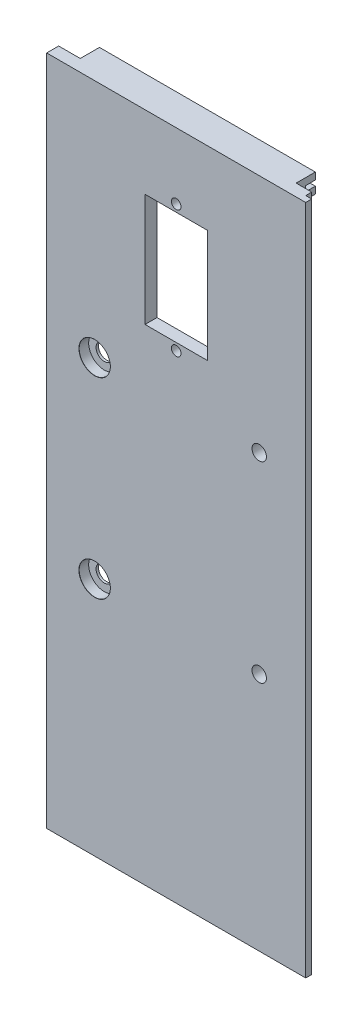
SolidWorks part; units mm, degrees
ref_plane "Plano frontal" through (0, 0, 0) normal (0, 0, 1) x (1, 0, 0)
ref_plane "Plano superior" through (0, 0, 0) normal (0, 1, 0) x (1, 0, 0)
ref_plane "Plano direito" through (0, 0, 0) normal (1, 0, 0) x (0, 0, -1)
other "Centro da massa"
sketch "Esboço1" plane through (0, 0, 0) normal (0, 0, 1) x (1, 0, 0)
  line L1 (-15.8914, 40.0685) -> (38.1086, 40.0685)
  line L2 (-15.8914, 40.0685) -> (-15.8914, -99.9315)
  line L3 (-15.8914, -99.9315) -> (38.1086, -99.9315)
  line L4 (38.1086, 40.0685) -> (38.1086, -99.9315)
  dimension "D1" = 54
  dimension "D2" = 140
extrude "Ressalto-extrusão1" add sketch "Esboço1" along normal blind 2.5
sketch "Esboço2" plane through (0, 0, 0) normal (0, 0, -1) x (-1, 0, 0)
  line L0 (-38.1086, 40.0685) -> (15.8914, 40.0685) construction
  line L1 (-33.6086, 40.0685) -> (11.3914, 40.0685)
  line L2 (-33.6086, 40.0685) -> (-33.6086, 36.0685)
  line L3 (-33.6086, 36.0685) -> (11.3914, 36.0685)
  line L4 (11.3914, 40.0685) -> (11.3914, 36.0685)
  line L5 (11.3914, 40.0685) -> (15.8914, 40.0685) construction
  line L6 (-38.1086, 40.0685) -> (-33.6086, 40.0685) construction
  dimension "D1" = 45
  dimension "D2" = 4
extrude "Ressalto-extrusão2" add sketch "Esboço2" along normal blind 4
fillet "Filete1" radius 2 1 edges at (11.1086, 36.0685, 0)
sketch "Esboço3" plane through (0, 0, -4) normal (0, 0, -1) x (-1, 0, 0)
  line L0 (-33.6086, 40.0685) -> (-33.6086, 34.0685) construction
  line L1 (-33.6086, 38.6185) -> (11.3914, 38.6185)
  line L2 (-33.6086, 38.6185) -> (-33.6086, 37.5185)
  line L3 (-33.6086, 37.5185) -> (11.3914, 37.5185)
  line L4 (11.3914, 38.6185) -> (11.3914, 37.5185)
  line L6 (11.3914, 40.0685) -> (11.3914, 38.6185) construction
  line L7 (11.3914, 37.5185) -> (11.3914, 36.0685) construction
  dimension "D1" = 1.1
extrude "Corte-extrusão1" cut sketch "Esboço3" against normal blind 2
sketch "Esboço4" plane through (0, 0, 0) normal (0, 0, -1) x (-1, 0, 0)
  line L0 (-38.1086, -29.9315) -> (15.8914, -29.9315) construction
  line L1 (-38.1086, -99.9315) -> (-38.1086, 40.0685) construction
  line L2 (15.8914, 40.0685) -> (15.8914, -99.9315) construction
  line L3 (-11.1086, 40.0685) -> (-11.1086, -99.9315) construction
  line L4 (11.3914, 40.0685) -> (-33.6086, 40.0685) construction
  line L5 (15.8914, -99.9315) -> (-38.1086, -99.9315) construction
  line L6 (5.8914, 40.0685) -> (5.8914, -99.9315) construction
  circle A0 centre (5.8914, -9.9315) radius 3.9278
  circle A1 centre (5.8914, -49.9315) radius 3.9278
  circle A3 centre (-28.4086, -9.9315) radius 3.9278
  circle A4 centre (-28.4086, -49.9315) radius 3.9278
  dimension "D1" = 10
  dimension "D2" = 20
  dimension "D3" = 9.7
hole_wizard "Rebaixo para parafuso com cabeça redonda de M31" positions "Esboço5" profile "Esboço6" counterbore size "M3" standard "ISO" end condition through all
sketch "Esboço5" plane through (0, 0, 2.5) normal (0, 0, 1) x (1, 0, 0)
  point P0 (-5.8914, -9.9315)
  point P3 (-5.8914, -49.9315)
sketch "Esboço6" plane through (-5.8914, -9.9315, 2.5) normal (1, 0, 0) x (0, -1, 0)
  line L0 (0, 0) -> (0, 6.5)
  line L1 (0, 6.5) -> (1.7, 6.5)
  line L3 (1.7, 6.5) -> (1.7, 2)
  line L4 (3.25, 2) -> (1.7, 2)
  line L5 (3.25, 2) -> (3.25, 0.025)
  line L6 (3.25, 0.025) -> (3.275, 0)
  line L7 (3.275, 0) -> (0, 0)
  line L8 (-3.25, 0.025) -> (-3.275, 0) construction
  line L11 (0, -6.35) -> (0, 107.95) construction
  dimension "Thru Hole Dia." = 3.4
  dimension "Thru Hole Depth" = 6.5
  dimension "C'Bore Dia." = 6.5
  dimension "C'Bore Depth" = 2
  dimension "Near C'Sink Dia." = 6.55
  dimension "Near C'Sink Angle" = 90
sketch "Esboço7" plane through (0, 0, 2.5) normal (0, 0, 1) x (1, 0, 0)
  line L0 (11.1086, 40.0685) -> (11.1086, -99.9315) construction
  line L1 (4.6086, 24.7988) -> (17.6086, 24.7988)
  line L2 (4.6086, 24.7988) -> (4.6086, 1.2988)
  line L3 (4.6086, 1.2988) -> (17.6086, 1.2988)
  line L4 (17.6086, 24.7988) -> (17.6086, 1.2988)
  line L5 (4.6086, 13.0488) -> (17.6086, 13.0488) construction
  circle A0 centre (11.1086, 26.2988) radius 1
  circle A1 centre (11.1086, -0.2012) radius 1
  point P4 (11.1086, 24.7988)
  point P11 (11.1086, 27.2988)
  dimension "D3" = 2
  dimension "D1" = 13
  dimension "D2" = 23.5
  dimension "D4" = 2.5
extrude "Corte-extrusão2" cut sketch "Esboço7" against normal through all contours A0 | L2 L1 L4 L3 | A1
sketch "Esboço8" plane through (0, 0, 0) normal (0, 0, -1) x (-1, 0, 0)
  line L1 (-18.2699, 0) -> (-22.2699, 0)
  line L2 (-18.2699, 0) -> (-18.2699, -60)
  line L3 (-18.2699, -60) -> (-22.2699, -60)
  line L4 (-22.2699, 0) -> (-22.2699, -60)
  dimension "D1" = 4
  dimension "D2" = 60
extrude "Ressalto-extrusão3" add sketch "Esboço8" along normal blind 7.5
sketch "Esboço9" plane through (0, 0, -7.5) normal (0, 0, -1) x (-1, 0, 0)
  line L0 (-18.2699, 0) -> (-22.2699, 0) construction
  line L1 (-21.2699, 0) -> (-19.2699, 0)
  line L2 (-21.2699, 0) -> (-21.2699, -58)
  line L3 (-21.2699, -58) -> (-19.2699, -58)
  line L4 (-19.2699, 0) -> (-19.2699, -58)
  line L5 (-22.2699, -60) -> (-18.2699, -60) construction
  line L6 (-22.2699, 0) -> (-21.2699, 0) construction
  line L7 (-19.2699, 0) -> (-18.2699, 0) construction
  dimension "D1" = 2
  dimension "D2" = 2
extrude "Corte-extrusão3" cut sketch "Esboço9" against normal blind 2
sketch "Esboço11" plane through (0, 0, -7.5) normal (0, 0, -1) x (-1, 0, 0)
  line L0 (-18.2699, -60) -> (-18.2699, 0) construction
  line L1 (-22.2699, -60) -> (-18.2699, -60)
  line L2 (-22.2699, -60) -> (-22.2699, -52)
  line L3 (-22.2699, -52) -> (-18.2699, -52)
  line L4 (-18.2699, -60) -> (-18.2699, -52)
  dimension "D1" = 8
extrude "Ressalto-extrusão4" add sketch "Esboço11" along normal blind 4
sketch "Esboço12" plane through (0, -52, 0) normal (0, 1, 0) x (1, 0, 0)
  line L0 (18.2699, 11.5) -> (22.2699, 11.5) construction
  line L1 (19.2699, 7.5) -> (21.2699, 7.5)
  line L2 (19.2699, 7.5) -> (19.2699, 11.5)
  line L3 (19.2699, 11.5) -> (21.2699, 11.5)
  line L4 (21.2699, 7.5) -> (21.2699, 11.5)
  dimension "D1" = 2
extrude "Corte-extrusão5" cut sketch "Esboço12" against normal blind 6
sketch "Esboço13" plane through (22.2699, 0, 0) normal (1, 0, 0) x (0, 0, -1)
  line L0 (11.5, -58) -> (3.9881, -58) construction
  line L1 (3.9881, -58) -> (7.5, -52) construction
  line L2 (0, 0) -> (0, -60) construction
  circle A0 centre (8.5, -55) radius 1.6
  dimension "D1" = 3.2
  dimension "D2" = 3
  dimension "D3" = 8.5
extrude "Corte-extrusão6" cut sketch "Esboço13" against normal blind 4
fillet "Filete2" radius 2 2 edges at (18.7699, -52, -7.5) (21.7699, -52, -7.5)
ref_plane "Plano1" through (0, 0, -10) normal (0, 0, -1) x (-1, 0, 0)
fillet "Filete3" radius 2 1 edges at (20.2699, -60, 0)
fillet "Filete4" radius 2 2 edges at (18.2699, -31, 0) (22.2699, -31, 0)
sketch "Esboço16" plane through (0, 0, 0) normal (0, 0, -1) x (-1, 0, 0)
  line L0 (15.8914, -99.9315) -> (-38.1086, -99.9315) construction
  line L1 (-38.1086, 40.0685) -> (-36.8586, 40.0685)
  line L2 (-38.1086, 40.0685) -> (-38.1086, -99.9315)
  line L3 (-38.1086, -99.9315) -> (-36.8586, -99.9315)
  line L4 (-36.8586, 40.0685) -> (-36.8586, -99.9315)
  dimension "D1" = 1.25
extrude "Corte-extrusão7" cut sketch "Esboço16" against normal blind 1.25
hole_wizard "Furos-guia com Ø3.0mm2" positions "Esboço17" profile "Esboço18" hole size "Ø3.0" standard "ISO" end condition through all
sketch "Esboço17" plane through (0, 0, 0) normal (0, 0, -1) x (-1, 0, 0)
  point P0 (-28.4086, -9.9315)
  point P3 (-28.4086, -49.9315)
sketch "Esboço18" plane through (28.4086, -9.9315, 0) normal (1, 0, 0) x (0, 1, 0)
  line L0 (0, 0) -> (0, 2.5)
  line L1 (0, 2.5) -> (1.5, 2.5)
  line L2 (1.5, 2.5) -> (1.5, 0.025)
  line L3 (1.5, 0.025) -> (1.525, 0)
  line L5 (1.525, 0) -> (0, 0)
  line L6 (-1.5, 0.025) -> (-1.525, 0) construction
  line L11 (0, -6.35) -> (0, 107.95) construction
  dimension "Thru Hole Dia." = 3
  dimension "Thru Hole Depth" = 2.5
  dimension "Near C'Sink Dia." = 3.05
  dimension "Near C'Sink Angle" = 90
